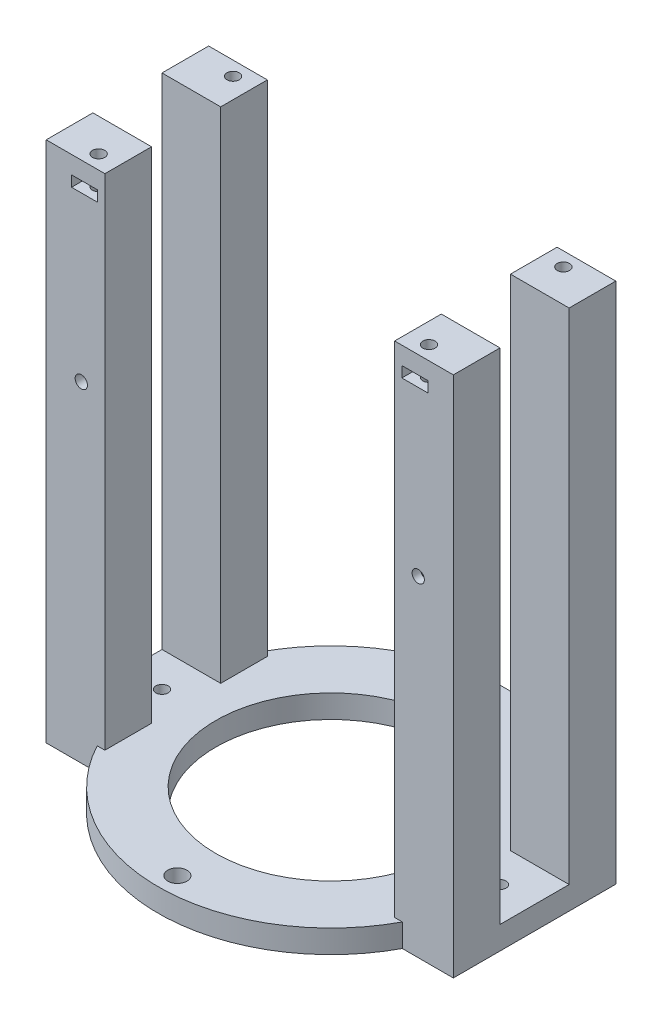
SolidWorks part; units mm, degrees
ref_plane "Front Plane" through (0, 0, 0) normal (0, 0, 1) x (1, 0, 0)
ref_plane "Top Plane" through (0, 0, 0) normal (0, 1, 0) x (1, 0, 0)
ref_plane "Right Plane" through (0, 0, 0) normal (1, 0, 0) x (0, 0, -1)
sketch "Sketch1" plane through (0, 0, 0) normal (0, 1, 0) x (1, 0, 0)
  line L0 (33, 0) -> (-33, 0) construction
  line L2 (-16, 21.15) -> (-50, 21.15)
  line L3 (-16, 21.15) -> (-16, -21.15)
  line L4 (-16, -21.15) -> (-50, -21.15)
  line L5 (-50, 21.15) -> (-50, -21.15)
  line L6 (-16, 21.15) -> (-50, -21.15) construction
  line L7 (-16, -21.15) -> (-50, 21.15) construction
  line L8 (16, 21.15) -> (50, 21.15)
  line L9 (16, 21.15) -> (16, -21.15)
  line L10 (16, -21.15) -> (50, -21.15)
  line L11 (50, 21.15) -> (50, -21.15)
  line L12 (16, 21.15) -> (50, -21.15) construction
  line L13 (16, -21.15) -> (50, 21.15) construction
  circle A0 centre (0, 0) radius 45
  point P6 (0, 0)
  dimension "D1" = 90
  dimension "D2" = 66
  dimension "D3" = 42.3
  dimension "D4" = 42.3
  dimension "D5" = 34
  dimension "D6" = 34
extrude "body" add sketch "Sketch1" along normal blind 6 contours A0 L2 L5 L4 | L2 A0 L4 L3 | L8 A0 L2 L3 L4 L10 L9 | L10 A0 L8 L9 | A0 L10 L11 L8
sketch "Sketch2" plane through (0, 6, 0) normal (0, 1, 0) x (1, 0, 0)
  line L0 (39.72, -21.15) -> (39.72, 21.15)
  line L1 (-50, 21.15) -> (-39.72, 21.15)
  line L2 (-50, 21.15) -> (-50, -21.15)
  line L3 (-50, -21.15) -> (-39.72, -21.15)
  line L4 (-39.72, 21.15) -> (-39.72, -21.15)
  line L5 (50, 21.15) -> (39.72, 21.15)
  line L6 (50, 21.15) -> (50, -21.15)
  line L7 (50, -21.15) -> (39.72, -21.15)
  line L8 (39.72, 21.15) -> (39.72, -21.15)
  line L9 (39.72, -21.15) -> (37.72, -21.15)
  line L10 (39.72, 21.15) -> (37.72, 21.15)
  line L11 (37.72, -21.15) -> (37.72, 21.15)
  line L12 (-39.72, -21.15) -> (-39.72, 21.15)
  line L13 (-39.72, -21.15) -> (-37.72, -21.15)
  line L14 (-39.72, 21.15) -> (-37.72, 21.15)
  line L15 (-37.72, -21.15) -> (-37.72, 21.15)
  line M6 (39.72, -21.15) -> (50, -21.15)
  line M7 (50, -21.15) -> (50, 21.15)
  line M8 (50, 21.15) -> (39.72, 21.15)
  dimension "D1" = 2
  dimension "D2" = 2
extrude "wings" add sketch "Sketch2" along normal blind 130 contours L8 M8 M6 M7 | L2 L1 L4 L3 | L12 L13 L15 L14 | L0 L9 L11 L10
sketch "Sketch3" plane through (0, 136, 0) normal (0, 1, 0) x (1, 0, 0)
  line L0 (43, 0) -> (-43, 0) construction
  line L1 (43, -17.5) -> (43, 17.5) construction
  line L2 (-43, -17.5) -> (-43, 17.5) construction
  circle A0 centre (43, -17.5) radius 1.6
  circle A1 centre (-43, -17.5) radius 1.6
  circle A2 centre (-43, 17.5) radius 1.6
  circle A3 centre (43, 17.5) radius 1.6
  point P4 (0, 0)
  point P8 (43, 0)
  point P11 (-43, 0)
  dimension "D4" = 3.2
  dimension "D5" = 3.2
  dimension "D6" = 3.2
  dimension "D7" = 3.2
  dimension "D1" = 86
  dimension "D2" = 35
  dimension "D3" = 35
extrude "mounting-bore" cut sketch "Sketch3" against normal through all
sketch "Sketch5" plane through (50, 0, 0) normal (1, 0, 0) x (0, 0, -1)
  line L0 (0, 0) -> (0, 6)
  line L1 (21.15, 0) -> (-21.15, 0) construction
  line L2 (9, 6) -> (-9, 6)
  line L3 (9, 6) -> (-9, 6)
  line L4 (9, 6) -> (9, 136)
  line L5 (-9, 6) -> (-9, 136)
  line L6 (9, 136) -> (-9, 136)
  point P7 (0, 6)
  line M9 (21.15, 136) -> (-21.15, 136)
  dimension "D1" = 6
  dimension "D2" = 18
  dimension "D3" = 130
extrude "cut-excess-material" cut sketch "Sketch5" against normal through all contours L5 L2 L4 M9
sketch "Sketch6" plane through (0, 0, 0) normal (0, -1, 0) x (1, 0, 0)
  line L0 (-44, 0) -> (44, 0)
  circle A0 centre (-44, 0) radius 1.6
  circle A1 centre (44, 0) radius 1.6
  point P4 (0, 0)
  dimension "D2" = 3.2
  dimension "D3" = 3.2
  dimension "D1" = 88
extrude "cut-battery-mount" cut sketch "Sketch6" against normal up to next
sketch "Sketch8" plane through (0, 0, 21.15) normal (0, 0, 1) x (1, 0, 0)
  line L1 (37.72, 136) -> (50, 136) construction
  line L2 (43, 136) -> (43, 130)
  line L3 (37.72, 136) -> (43, 136)
  line L4 (39.6, 131.4) -> (46.4, 131.4)
  line L5 (39.6, 131.4) -> (39.6, 128.6)
  line L6 (39.6, 128.6) -> (46.4, 128.6)
  line L7 (46.4, 131.4) -> (46.4, 128.6)
  line L8 (39.6, 131.4) -> (46.4, 128.6) construction
  line L9 (39.6, 128.6) -> (46.4, 131.4) construction
  dimension "D2" = 6
  dimension "D3" = 6.8
  dimension "D4" = 2.8
extrude "capture-nut-1" cut sketch "Sketch8" against normal blind 7.3 contours L5 L4 L7 L6
pattern_circular "CirPattern1" count 2 over 360 about axis through (0, 0, 0) along (0, 1, 0) of "capture-nut-1"
sketch "Sketch10" plane through (0, 0, -21.15) normal (0, 0, -1) x (-1, 0, 0)
  line L1 (-50, 136) -> (-37.72, 136) construction
  line L2 (-43, 136) -> (-43, 130)
  line L3 (-43, 136) -> (-37.72, 136)
  line L4 (-46.4, 131.4) -> (-39.6, 131.4)
  line L5 (-46.4, 131.4) -> (-46.4, 128.6)
  line L6 (-46.4, 128.6) -> (-39.6, 128.6)
  line L7 (-39.6, 131.4) -> (-39.6, 128.6)
  line L8 (-46.4, 131.4) -> (-39.6, 128.6) construction
  line L9 (-46.4, 128.6) -> (-39.6, 131.4) construction
  dimension "D2" = 6
  dimension "D3" = 6.8
  dimension "D4" = 2.8
extrude "capture-nut-2" cut sketch "Sketch10" against normal blind 7.3
pattern_circular "CirPattern2" count 2 over 360 about axis through (0, 0, 0) along (0, 1, 0) of "capture-nut-2"
sketch "Sketch11" plane through (0, 0, 0) normal (0, -1, 0) x (1, 0, 0)
  circle A0 centre (0, 0) radius 30
  dimension "D1" = 60
extrude "cut-center-hole" cut sketch "Sketch11" against normal up to next
sketch "Sketch12" plane through (0, 0, 0) normal (0, -1, 0) x (1, 0, 0)
  line L0 (0, 40) -> (0, -40)
  circle A0 centre (0, -40) radius 2.5
  circle A1 centre (0, 40) radius 2.5
  point P5 (0, 0)
  dimension "D2" = 5
  dimension "D3" = 5
  dimension "D1" = 80
extrude "cut-harness-mount" cut sketch "Sketch12" against normal up to next
sketch "Sketch13" plane through (0, 128.6, 0) normal (0, 1, 0) x (1, 0, 0)
  line L0 (46.4, 17.5) -> (46.4, 13.85)
  line L1 (46.4, 17.5) -> (44.7, 20.4445)
  line L2 (44.7, 20.4445) -> (41.3, 20.4445)
  line L3 (41.3, 20.4445) -> (39.6, 17.5)
  line L4 (39.6, 17.5) -> (41.3, 14.5555)
  line L5 (41.3, 14.5555) -> (44.7, 14.5555)
  line L6 (44.7, 14.5555) -> (46.4, 17.5)
  line L7 (46.4, 13.85) -> (39.6, 13.85)
  line L9 (46.4, 13.85) -> (39.6, 13.85)
  line L10 (46.4, 13.85) -> (46.4, 17.5)
  line L11 (46.4, 17.5) -> (39.6, 17.5)
  line L12 (39.6, 13.85) -> (39.6, 17.5)
  circle A0 centre (43, 17.5) radius 2.9445 construction
extrude "captive-nut-wall-1" add sketch "Sketch13" along normal through all contours L12 L7 L11 L6 L5 L4
sketch "Sketch14" plane through (0, 128.6, 0) normal (0, 1, 0) x (1, 0, 0)
  line L1 (-39.6, 17.5) -> (-41.3, 20.4445)
  line L2 (-41.3, 20.4445) -> (-44.7, 20.4445)
  line L3 (-44.7, 20.4445) -> (-46.4, 17.5)
  line L4 (-46.4, 17.5) -> (-44.7, 14.5555)
  line L5 (-44.7, 14.5555) -> (-41.3, 14.5555)
  line L6 (-41.3, 14.5555) -> (-39.6, 17.5)
  line L7 (-39.6, 13.85) -> (-46.4, 13.85)
  line L8 (-39.6, 13.85) -> (-39.6, 17.5)
  line L9 (-39.6, 17.5) -> (-46.4, 17.5)
  line L10 (-46.4, 13.85) -> (-46.4, 17.5)
  circle A0 centre (-43, 17.5) radius 2.9445 construction
  line M6 (-46.4, 21.15) -> (-46.4, 13.85)
  line M7 (-46.4, 13.85) -> (-39.6, 13.85)
  line M8 (-39.6, 13.85) -> (-39.6, 21.15)
extrude "captive-nut-wall-2" add sketch "Sketch14" along normal through all contours L6 L5 L4 M6 M7 M8
sketch "Sketch16" plane through (0, 128.6, 0) normal (0, 1, 0) x (1, 0, 0)
  line L1 (-46.4, -17.5) -> (-44.7, -20.4445)
  line L2 (-44.7, -20.4445) -> (-41.3, -20.4445)
  line L3 (-41.3, -20.4445) -> (-39.6, -17.5)
  line L4 (-39.6, -17.5) -> (-41.3, -14.5555)
  line L5 (-41.3, -14.5555) -> (-44.7, -14.5555)
  line L6 (-44.7, -14.5555) -> (-46.4, -17.5)
  line L7 (-46.4, -13.85) -> (-39.6, -13.85)
  line L8 (-46.4, -13.85) -> (-46.4, -17.5)
  line L9 (-46.4, -17.5) -> (-39.6, -17.5)
  line L10 (-39.6, -13.85) -> (-39.6, -17.5)
  circle A0 centre (-43, -17.5) radius 2.9445 construction
  line M13 (-39.6, -13.85) -> (-46.4, -13.85)
  line M14 (-46.4, -13.85) -> (-46.4, -21.15)
extrude "captive-nut-wall-3" add sketch "Sketch16" along normal through all contours L10 L6 L5 L4 M13 M14
sketch "Sketch17" plane through (0, 128.6, 0) normal (0, 1, 0) x (1, 0, 0)
  line L1 (39.6, -17.5) -> (41.3, -20.4445)
  line L2 (41.3, -20.4445) -> (44.7, -20.4445)
  line L3 (44.7, -20.4445) -> (46.4, -17.5)
  line L4 (46.4, -17.5) -> (44.7, -14.5555)
  line L5 (44.7, -14.5555) -> (41.3, -14.5555)
  line L6 (41.3, -14.5555) -> (39.6, -17.5)
  line L7 (39.6, -13.85) -> (46.4, -13.85)
  line L8 (39.6, -13.85) -> (39.6, -17.5)
  line L9 (39.6, -17.5) -> (46.4, -17.5)
  line L10 (46.4, -13.85) -> (46.4, -17.5)
  circle A0 centre (43, -17.5) radius 2.9445 construction
  line M6 (46.4, -21.15) -> (46.4, -13.85)
  line M7 (46.4, -13.85) -> (39.6, -13.85)
  line M8 (39.6, -13.85) -> (39.6, -21.15)
extrude "captive-nut-wall-4" add sketch "Sketch17" along normal through all contours L6 L5 L4 M6 M7 M8
sketch "Sketch20" plane through (0, 0, 21.15) normal (0, 0, 1) x (1, 0, 0)
  line L0 (-43.86, 136) -> (-43.86, 86) construction
  line L1 (-50, 136) -> (-37.72, 136) construction
  line L3 (43.86, 136) -> (43.86, 86) construction
  line L4 (50, 136) -> (37.72, 136) construction
  circle A0 centre (-43.86, 86) radius 1.6
  circle A1 centre (43.86, 86) radius 1.6
  dimension "D3" = 3.2
  dimension "D4" = 3.2
  dimension "D1" = 50
  dimension "D2" = 50
extrude "middle-deck-holes" cut sketch "Sketch20" against normal up to next
sketch "Sketch21" plane through (0, 0, 9) normal (0, 0, -1) x (-1, 0, 0)
  line L1 (44.6094, 89.111) -> (41.5405, 88.2045)
  line L2 (41.5405, 88.2045) -> (40.7911, 85.0935)
  line L3 (40.7911, 85.0935) -> (43.1106, 82.889)
  line L4 (43.1106, 82.889) -> (46.1795, 83.7955)
  line L5 (46.1795, 83.7955) -> (46.9289, 86.9065)
  line L6 (46.9289, 86.9065) -> (44.6094, 89.111)
  line L7 (-43.1106, 89.111) -> (-46.1795, 88.2045)
  line L8 (-46.1795, 88.2045) -> (-46.9289, 85.0935)
  line L9 (-46.9289, 85.0935) -> (-44.6094, 82.889)
  line L10 (-44.6094, 82.889) -> (-41.5405, 83.7955)
  line L11 (-41.5405, 83.7955) -> (-40.7911, 86.9065)
  line L12 (-40.7911, 86.9065) -> (-43.1106, 89.111)
  circle A0 centre (43.86, 86) radius 2.7713 construction
  circle A1 centre (-43.86, 86) radius 2.7713 construction
  dimension "D1" = 6.4
  dimension "D2" = 6.4
extrude "middle-deck-captive-nut" cut sketch "Sketch21" against normal blind 2.5
sketch "Sketch22" plane through (50, 0, 0) normal (1, 0, 0) x (0, 0, -1)
  line L0 (21.15, 136) -> (9, 136)
  line L1 (9, 136) -> (9, 6)
  line L2 (9, 6) -> (-9, 6)
  line L3 (-9, 6) -> (-9, 136)
  line L4 (-9, 136) -> (-21.15, 136)
  line L5 (-21.15, 136) -> (-21.15, 0)
  line L6 (-21.15, 0) -> (21.15, 0)
  line L7 (21.15, 0) -> (21.15, 136)
extrude "wing-extra-width-1" add sketch "Sketch22" along normal blind 3
sketch "Sketch24" plane through (-50, 0, 0) normal (-1, 0, 0) x (0, 0, 1)
  line L0 (9, 136) -> (9, 6)
  line L1 (9, 6) -> (-9, 6)
  line L2 (-9, 6) -> (-9, 136)
  line L3 (-9, 136) -> (-21.15, 136)
  line L4 (-21.15, 136) -> (-21.15, 0)
  line L5 (-21.15, 0) -> (21.15, 0)
  line L6 (21.15, 0) -> (21.15, 136)
  line L7 (21.15, 136) -> (9, 136)
extrude "wing-extra-width-2" add sketch "Sketch24" along normal blind 3
equation "\"th\"= 6mm"
equation "\"D1@body\"=\"th\""
equation "\"wing\"= 130mm"
equation "\"D1@wings\"=\"wing\""
equation "\"D1@Sketch5\"=\"th\""
equation "\"D3@Sketch5\"=\"wing\""
equation "\"capture_nut_depth\"= 7.3mm"
equation "\"capture_nut_height\"= 2.8mm"
equation "\"capture_nut_width\"= 6.8mm"
equation "\"D3@Sketch8\"=\"capture_nut_width\""
equation "\"D4@Sketch8\"=\"capture_nut_height\""
equation "\"D1@capture-nut-1\" = \"capture_nut_depth\""
equation "\"D3@Sketch10\"=\"capture_nut_width\""
equation "\"D4@Sketch10\"=\"capture_nut_height\""
equation "\"D1@capture-nut-2\" = \"capture_nut_depth\""
